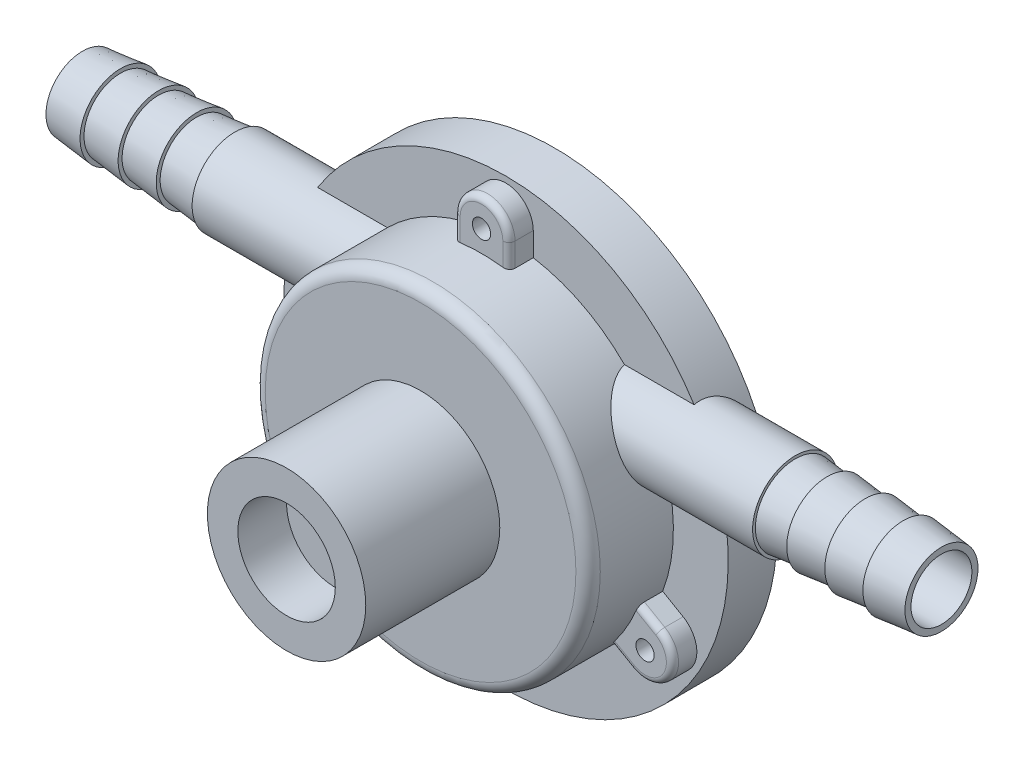
SolidWorks part; units mm, degrees
ref_plane "Front Plane" through (0, 0, 0) normal (0, 0, 1) x (1, 0, 0)
ref_plane "Top Plane" through (0, 0, 0) normal (0, 1, 0) x (1, 0, 0)
ref_plane "Right Plane" through (0, 0, 0) normal (1, 0, 0) x (0, 0, -1)
sketch "Sketch1" plane through (0, 0, 0) normal (0, 0, 1) x (1, 0, 0)
  circle A0 centre (0, 0) radius 36.5
  dimension "D1" = 73
extrude "Boss-Extrude1" add sketch "Sketch1" along normal blind 8
sketch "Sketch2" plane through (0, 0, 8) normal (0, 0, 1) x (1, 0, 0)
  circle A0 centre (0, 0) radius 27.5
  dimension "D1" = 55
extrude "Boss-Extrude2" add sketch "Sketch2" along normal blind 14
sketch "Sketch3" plane through (0, 0, 22) normal (0, 0, 1) x (1, 0, 0)
  circle A0 centre (0, 0) radius 13
  dimension "D1" = 26
extrude "Boss-Extrude3" add sketch "Sketch3" along normal blind 22
sketch "Sketch4" plane through (0, 0, 44) normal (0, 0, 1) x (1, 0, 0)
  circle A0 centre (0, 0) radius 8
  dimension "D1" = 16
extrude "Cut-Extrude1" cut sketch "Sketch4" against normal blind 8
ref_plane "Plane2" through (36.5, 0, 0) normal (1, 0, 0) x (0, 0, -1)
sketch "Sketch6" plane through (36.5, 0, 0) normal (1, 0, 0) x (0, 0, -1)
  line L0 (0, -36.5) -> (0, 36.5) construction
  line L2 (-8, 27.5) -> (-22, 27.5) construction
  circle A0 centre (-7, 12.5) radius 7
  dimension "D1" = 14
  dimension "D2" = 7
  dimension "D3" = 15
extrude "Boss-Extrude4" add sketch "Sketch6" along normal blind 10 and the other way blind 82
sketch "Sketch8" plane through (0, 0, 0) normal (0, 0, -1) x (-1, 0, 0)
  circle A1 centre (0, 0) radius 8 construction
  arc A3 (-17.6535, 13.95) -> (17.6535, 13.95) centre (0, 0) ccw
  arc A4 (-17.6535, 13.95) -> (17.6535, 13.95) centre (0, -22.5) cw
  point P2 (0, -8)
  dimension "D1" = 45
  dimension "D2" = 40.5
extrude "Cut-Extrude2" cut sketch "Sketch8" against normal blind 12
sketch "Sketch10" plane through (46.5, 0, 0) normal (1, 0, 0) x (0, 0, -1)
  circle A0 centre (-7, 12.5) radius 5
  dimension "D1" = 10
sketch "Sketch11" plane through (0, 0, 0) normal (0, 0, -1) x (-1, 0, 0)
  circle A0 centre (0, 31) radius 1.5
  circle A1 centre (0, 0) radius 36.5 construction
  circle A7 centre (26.8468, -15.5) radius 1.5
  circle A8 centre (-26.8468, -15.5) radius 1.5
  arc A9 (34.2929, 12.5) -> (-34.2929, 12.5) centre (0, 0) ccw construction
  point P13 (0, -1)
  point P14 (0, 0)
  point P15 (0, -1)
  dimension "D1" = 3
  dimension "D3" = 3
  dimension "D4" = 26.8468
  dimension "D5" = 31
  dimension "D2" = 31
extrude "Cut-Extrude4" cut sketch "Sketch11" against normal through all
fillet "Fillet1" radius 2 1 edges at (27.5, 0, 22)
extrude "Cut-Extrude5" cut sketch "Sketch10" against normal through all
sketch "Sketch12" plane through (0, 0, 36) normal (0, 0, 1) x (1, 0, 0)
  circle A0 centre (0, 0) radius 3.2
  dimension "D1" = 6.4
extrude "Cut-Extrude6" cut sketch "Sketch12" against normal through all
sketch "Sketch13" plane through (0, 0, 0) normal (0, 0, -1) x (-1, 0, 0)
  circle A0 centre (0, 0) radius 25
  circle A1 centre (0, 0) radius 27.3
extrude "Cut-Extrude7" cut sketch "Sketch13" against normal blind 1.2
sketch "Sketch14" plane through (0, 0, 8) normal (0, 0, 1) x (1, 0, 0)
  line L0 (4.5, 31) -> (4.5, 27.1293)
  line L1 (-4.5, 31) -> (-4.5, 27.1293)
  line L2 (29.0968, -11.6029) -> (25.7447, -9.6675)
  line L3 (24.5968, -19.3971) -> (21.2447, -17.4618)
  line L4 (-24.5968, -19.3971) -> (-21.2447, -17.4618)
  line L5 (-29.0968, -11.6029) -> (-25.7447, -9.6675)
  arc A2 (4.5, 31) -> (-4.5, 31) centre (0, 31) ccw
  arc A3 (19.4627, 19.4282) -> (-19.4627, 19.4282) centre (0, 0) ccw construction
  arc A4 (24.5968, -19.3971) -> (29.0968, -11.6029) centre (26.8468, -15.5) ccw
  arc A5 (-29.0968, -11.6029) -> (-24.5968, -19.3971) centre (-26.8468, -15.5) ccw
  arc A6 (21.2447, -17.4618) -> (25.7447, -9.6675) centre (0, 0) ccw
  arc A7 (-25.7447, -9.6675) -> (-21.2447, -17.4618) centre (0, 0) ccw
  arc A8 (4.5, 27.1293) -> (-4.5, 27.1293) centre (0, 0) ccw
  point P27 (0, 0)
  dimension "D1" = 9
  dimension "D2" = 3
extrude "Boss-Extrude5" add sketch "Sketch14" along normal blind 4
fillet "Fillet2" radius 1 9 edges at (4.5, 29.0647, 12) (-4.5, 29.0647, 12) (22.9207, -18.4294, 12) (27.4207, -10.6352, 12) (-27.4207, -10.6352, 12) (-22.9207, -18.4294, 12) (0, 35.5, 12) (30.7439, -17.75, 12) (-30.7439, -17.75, 12)
sketch "Sketch15" plane through (0, 0, 0) normal (0, 0, -1) x (-1, 0, 0)
  circle A0 centre (0, 31) radius 1.5
  circle A1 centre (26.8468, -15.5) radius 1.5
  circle A2 centre (-26.8468, -15.5) radius 1.5
  point P10 (0, 0)
  dimension "D1" = 3
  dimension "D4" = 26.8468
  dimension "D3" = 15.5
  dimension "D2" = 3
extrude "Cut-Extrude8" cut sketch "Sketch15" against normal through all
ref_plane "Plane3" through (0, 12.5, 0) normal (0, 1, 0) x (1, 0, 0)
sketch "Sketch16" plane through (0, 12.5, 0) normal (0, 1, 0) x (1, 0, 0)
  line L0 (-70.5, -13) -> (-64.25, -13.65)
  line L3 (-45.5, 0) -> (-45.5, -14) construction
  line L4 (-70.5, -1) -> (-45.5, -1) construction
  line L5 (0, 0) -> (0, -60.1535) construction
  line L6 (70.5, -13) -> (70.5, -7)
  line L7 (-64.25, -13.65) -> (-64.25, -13)
  line L8 (-64.25, -13) -> (-58, -13.65)
  line L9 (-58, -13.65) -> (-58, -13)
  line L10 (-58, -13) -> (-51.75, -13.65)
  line L11 (-51.75, -13.65) -> (-51.75, -13)
  line L12 (-51.75, -13) -> (-45.5, -13.65)
  line L13 (-45.5, -13.65) -> (-45.5, -13)
  line L14 (70.5, -7) -> (45.5, -7)
  line L15 (-70.5, -7) -> (-45.5, -7)
  line L16 (-70.5, -13) -> (-70.5, -7)
  line L17 (-45.5, -7) -> (-45.5, -13)
  line L18 (45.5, -7) -> (45.5, -13)
  line L19 (45.5, -13.65) -> (45.5, -13)
  line L20 (51.75, -13) -> (45.5, -13.65)
  line L21 (51.75, -13.65) -> (51.75, -13)
  line L22 (58, -13) -> (51.75, -13.65)
  line L23 (58, -13.65) -> (58, -13)
  line L24 (64.25, -13) -> (58, -13.65)
  line L25 (64.25, -13.65) -> (64.25, -13)
  line L26 (70.5, -13) -> (64.25, -13.65)
  point P0 (-45.5, -7)
  line B0 (-70.5, -13) -> (-70.5, -1) construction
  line B1 (-70.5, -13) -> (-45.5, -13) construction
  line B2 (-45.5, -13) -> (-45.5, -1) construction
  line B3 (-70.5, -13) -> (-45.5, -1) construction
  line B4 (-45.5, -13) -> (-70.5, -1) construction
  line B5 (-68.289, -13.65) -> (-41.9667, -13.65) construction
  line B6 (-58, -7) -> (-26.614, -7) construction
  line B7 (-70.5, -12.2) -> (-45.5, -12.2)
sketch_block_instance "Block1-1"
sketch_block "Block1" parameters "D1"=12, "D2"=25, "D3"=0.65, "D4"=0.8
revolve "Revolve1" add sketch "Sketch16" angle 360 about L14 region at (-57.6991, 12.5, 12.7781) region at (-58, 12.5, 9.6)
sketch "Sketch17" plane through (70.5, 0, 0) normal (1, 0, 0) x (0, 0, -1)
  circle A0 centre (-7, 12.5) radius 5
extrude "Cut-Extrude9" cut sketch "Sketch17" against normal through all
